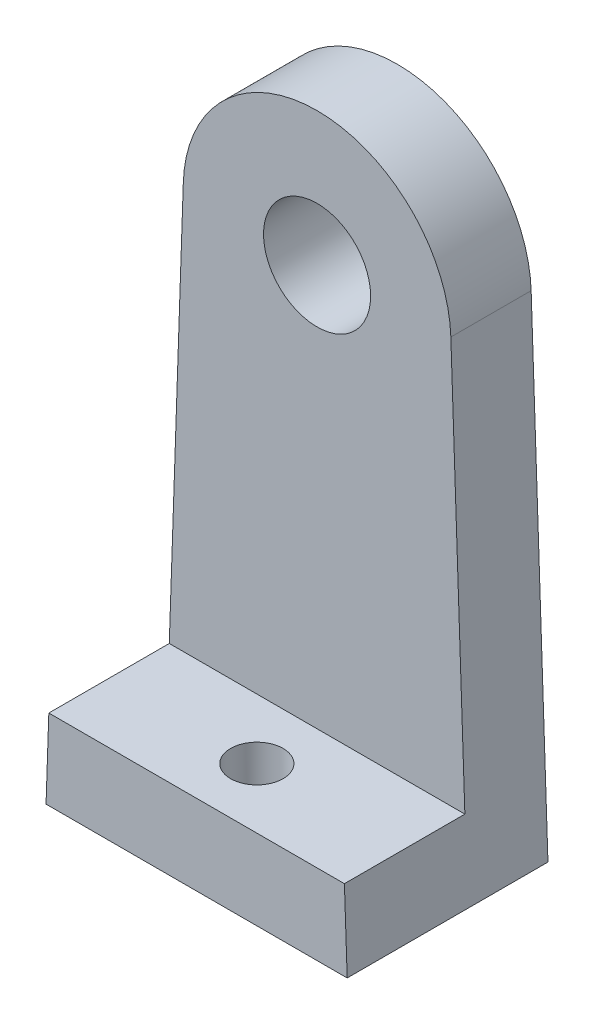
SolidWorks part; units mm, degrees
material "Gray Cast Iron"
ref_plane "Front Plane" through (0, 0, 0) normal (0, 0, 1) x (1, 0, 0)
ref_plane "Top Plane" through (0, 0, 0) normal (0, 1, 0) x (1, 0, 0)
ref_plane "Right Plane" through (0, 0, 0) normal (1, 0, 0) x (0, 0, -1)
sketch "Sketch1" plane through (0, 0, 0) normal (0, 0, 1) x (1, 0, 0)
  line L0 (-14.2875, 0) -> (14.2875, 0)
  line L1 (14.2875, 0) -> (12.6924, 46.1586)
  line L2 (-12.6924, 46.1586) -> (-14.2875, 0)
  arc A0 (12.6924, 46.1586) -> (-12.6924, 46.1586) centre (0, 45.72) ccw
  dimension "D4" = 12.7
  dimension "D1" = 14.2875
  dimension "D2" = 28.575
  dimension "D3" = 45.72
extrude "Boss-Extrude1" add sketch "Sketch1" along normal mid plane 7.62
sketch "Sketch2" plane through (0, 0, 0) normal (0, 0, 1) x (1, 0, 0)
  line L0 (-14.2875, 0) -> (14.2875, 0)
  line L1 (14.2875, 0) -> (14.0242, 7.62)
  line L2 (14.0242, 7.62) -> (-14.0242, 7.62)
  line L3 (-14.0242, 7.62) -> (-14.2875, 0)
  dimension "D1" = 14.2875
  dimension "D2" = 28.575
  dimension "D3" = 0.2633
  dimension "D4" = 7.62
  dimension "D5" = 28.0484
extrude "Boss-Extrude2" add sketch "Sketch2" along normal blind 11.43 from offset 3.81
sketch "Sketch3" plane through (0, 0, 0) normal (0, 0, 1) x (1, 0, 0)
  circle A0 centre (0, 45.72) radius 5.08
  dimension "D2" = 10.16
  dimension "D1" = 45.72
extrude "Cut-Extrude1" cut sketch "Sketch3" against normal mid plane 40
sketch "Sketch4" plane through (0, 0, 0) normal (0, 1, 0) x (1, 0, 0)
  circle A0 centre (0, -9.525) radius 2.4892
  dimension "D2" = 4.9784
  dimension "D1" = 9.525
extrude "Cut-Extrude2" cut sketch "Sketch4" against normal mid plane 40
